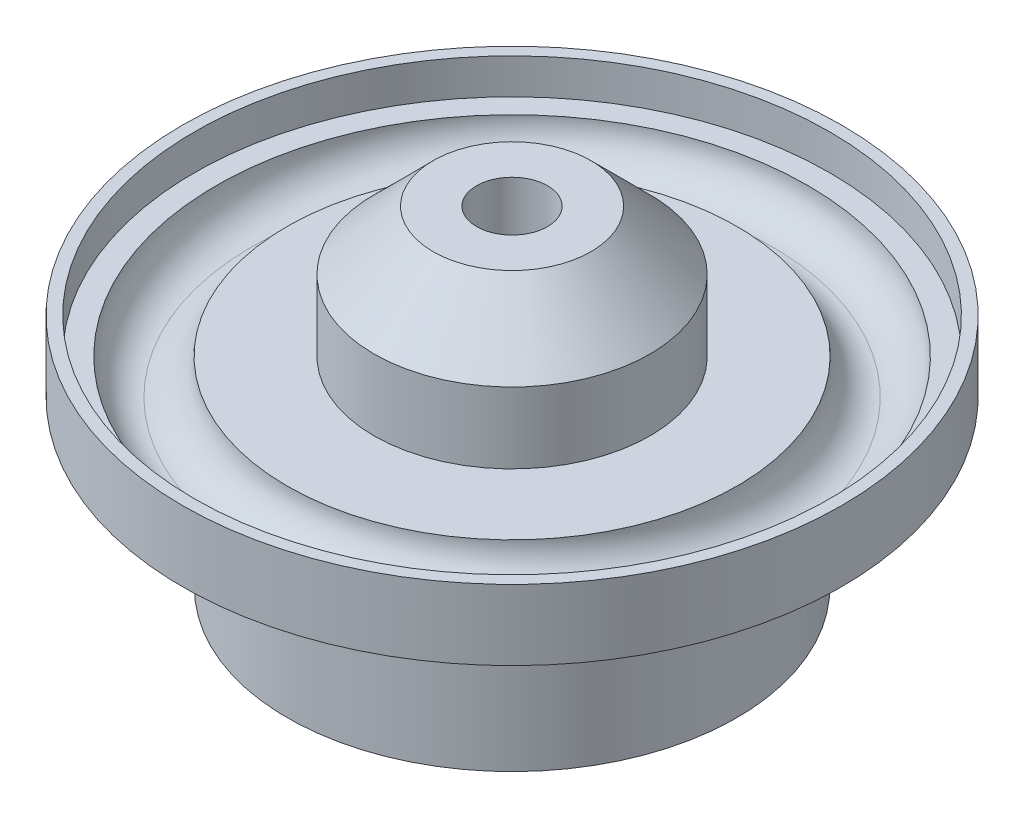
SolidWorks part; units mm, degrees
note: The reader was unsure of these and kept them because the rebuilt part matched: shared geometry of "Sketch2<5>".
ref_plane "Front" through (0, 0, 0) normal (0, 0, 1) x (1, 0, 0)
ref_plane "Top" through (0, 0, 0) normal (0, 1, 0) x (1, 0, 0)
ref_plane "Right" through (0, 0, 0) normal (1, 0, 0) x (0, 0, -1)
sketch "Sketch1" plane through (0, 0, 0) normal (0, 1, 0) x (1, 0, 0)
  line L1 (-15.55, -15.55) -> (15.55, -15.55) construction
  line L2 (-15.55, -15.55) -> (-15.55, 15.55) construction
  line L3 (-15.55, 15.55) -> (15.55, 15.55) construction
  line L4 (15.55, -15.55) -> (15.55, 15.55) construction
  line L5 (-15.55, -15.55) -> (15.55, 15.55) construction
  line L6 (-15.55, 15.55) -> (15.55, -15.55) construction
  circle A0 centre (0, 0) radius 27.8896
  circle A1 centre (0, 0) radius 3
  circle A2 centre (15.55, 15.55) radius 1.5 construction
  circle A3 centre (15.55, -15.55) radius 1.5 construction
  circle A4 centre (-15.55, -15.55) radius 1.5 construction
  circle A5 centre (-15.55, 15.55) radius 1.5 construction
  circle A6 centre (0, 0) radius 27.8896 construction
  dimension "D2" = 3
  dimension "D3" = 6
  dimension "D1" = 31.1
extrude "Boss-Extrude1" add sketch "Sketch1" along normal blind 20 contours A0
sketch "Sketch2" plane through (0, 20, 0) normal (0, 1, 0) x (1, 0, 0)
  line L1 (18.357, 18.357) -> (-18.357, 18.357) construction
  line L2 (18.357, 18.357) -> (18.357, -18.357) construction
  line L3 (18.357, -18.357) -> (-18.357, -18.357) construction
  line L4 (-18.357, 18.357) -> (-18.357, -18.357) construction
  line L5 (18.357, 18.357) -> (-18.357, -18.357) construction
  line L6 (18.357, -18.357) -> (-18.357, 18.357) construction
  circle A0 centre (-18.357, 18.357) radius 0.9289 construction
  circle A1 centre (-18.357, -18.357) radius 0.9289 construction
  circle A2 centre (18.357, 18.357) radius 0.9289 construction
  circle A3 centre (18.357, -18.357) radius 0.9289 construction
  circle A4 centre (0, 0) radius 26.8896
  circle A5 centre (0, 0) radius 25.0318
  circle A6 centre (0, 0) radius 27.8896 construction
  circle A7 centre (0, 0) radius 26.8896 construction
  circle A10 centre (0, 0) radius 19.0318
  circle A11 centre (0, 0) radius 25.0318 construction
  circle A12 centre (0, 0) radius 19.0318 construction
extrude "Cut-Extrude1" cut sketch "Sketch2" against normal blind 3
sketch "Sketch3" plane through (0, 20, 0) normal (0, 1, 0) x (1, 0, 0)
  circle A0 centre (-11.2498, -25.7784) radius 3
  circle A1 centre (0, 0) radius 28.1262
  dimension "D1" = 6
extrude "Cut-Extrude2" cut sketch "Sketch2<5>" against normal blind 6 contours A5 A10
sketch "Sketch2<5>" plane through (0, 20, 0) normal (0, 1, 0) x (1, 0, 0) same geometry as "Sketch2"
fillet "Fillet1" radius 3 2 edges at (0, 14, 25.0318) (0, 14, 19.0318)
sketch "Sketch4" plane through (0, 17, 0) normal (0, 1, 0) x (1, 0, 0)
  circle A0 centre (0, 0) radius 3
  circle A1 centre (0, 0) radius 11.6781
  circle A2 centre (0, 0) radius 11.6781 construction
extrude "Boss-Extrude2" add sketch "Sketch4" along normal blind 11
chamfer "Chamfer1" distance 5 angle 45 1 edges at (0, 28, 11.6781)
sketch "Sketch5" plane through (0, 0, 0) normal (0, -1, 0) x (1, 0, 0)
  circle A0 centre (0, 0) radius 19.0099
  circle A1 centre (0, 0) radius 27.8896
extrude "Cut-Extrude3" cut sketch "Sketch5" against normal blind 10
chamfer "Chamfer2" distance 6 angle 34 1 edges at (0, 10, -27.8896) first distance on face at (0, 10, -19.0099)
